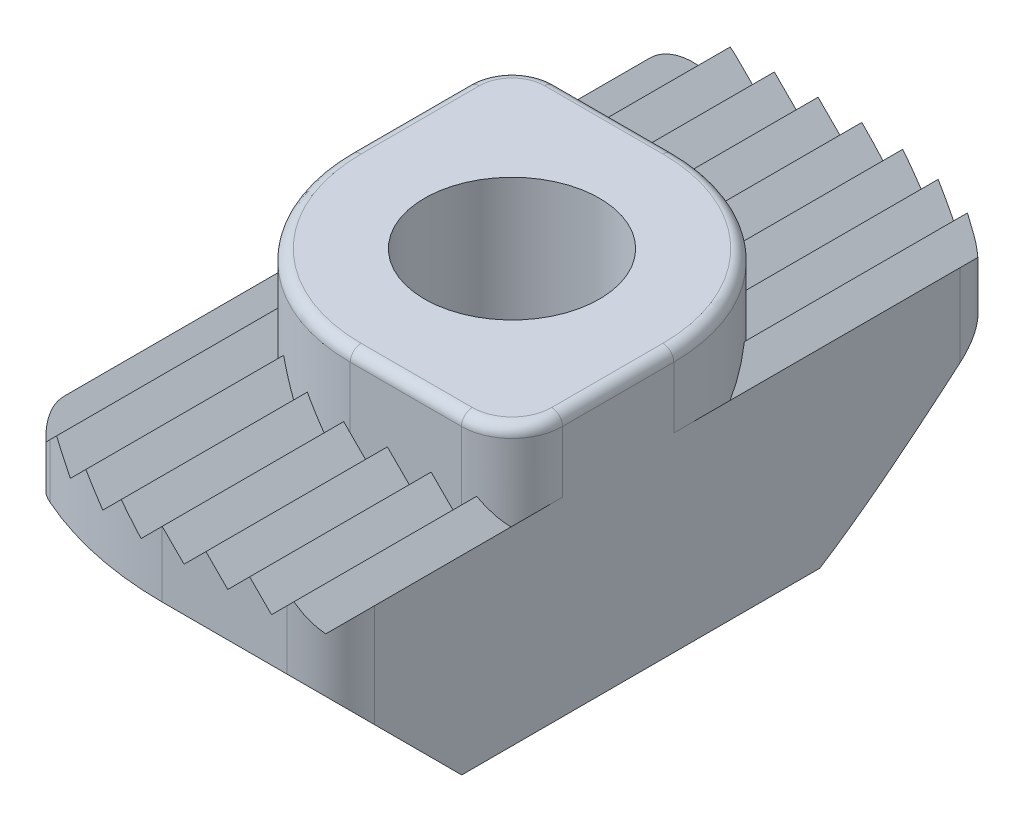
SolidWorks part; units mm, degrees
material "AISI 1020"
ref_plane "Front Plane" through (0, 0, 0) normal (0, 0, 1) x (1, 0, 0)
ref_plane "Top Plane" through (0, 0, 0) normal (0, 1, 0) x (1, 0, 0)
ref_plane "Right Plane" through (0, 0, 0) normal (1, 0, 0) x (0, 0, -1)
sketch "Sketch1" plane through (0, 0, 0) normal (0, 1, 0) x (1, 0, 0)
  line L0 (0, -8) -> (2.85, -8)
  line L1 (3.85, -7) -> (3.85, 6.3936)
  line L2 (0, 8) -> (-2.85, 8)
  line L3 (-3.85, 7) -> (-3.85, -6.3936)
  arc A0 (-3.85, -6.3936) -> (-3.2571, -7.3069) centre (-2.85, -6.3936) ccw
  arc A1 (-3.2571, -7.3069) -> (0, -8) centre (0, 0) ccw
  arc A2 (2.85, -8) -> (3.85, -7) centre (2.85, -7) ccw
  arc A3 (3.85, 6.3936) -> (3.2571, 7.3069) centre (2.85, 6.3936) ccw
  arc A4 (3.2571, 7.3069) -> (0, 8) centre (0, 0) ccw
  arc A5 (-2.85, 8) -> (-3.85, 7) centre (-2.85, 7) ccw
extrude "Extrude1" add sketch "Sketch1" along normal blind 4.5
sketch "Sketch2" plane through (0, 0, 0) normal (0, 0, 1) x (1, 0, 0)
  line L0 (-4, 4.5) -> (-3.5, 4)
  line L1 (-3.5, 4) -> (-3, 4.5)
  line L2 (-3, 4.5) -> (-2.5, 4)
  line L3 (-2.5, 4) -> (-2, 4.5)
  line L4 (-2, 4.5) -> (-1.5, 4)
  line L5 (-1.5, 4) -> (-1, 4.5)
  line L6 (-1, 4.5) -> (-0.5, 4)
  line L7 (-0.5, 4) -> (0, 4.5)
  line L8 (0, 4.5) -> (0.5, 4)
  line L9 (0.5, 4) -> (1, 4.5)
  line L10 (1, 4.5) -> (1.5, 4)
  line L11 (1.5, 4) -> (2, 4.5)
  line L12 (2, 4.5) -> (2.5, 4)
  line L13 (2.5, 4) -> (3, 4.5)
  line L14 (3, 4.5) -> (3.5, 4)
  line L15 (3.5, 4) -> (4, 4.5)
  line L16 (4, 4.5) -> (4, 5.5)
  line L17 (4, 5.5) -> (-4, 5.5)
  line L18 (-4, 5.5) -> (-4, 4.5)
extrude "Cut-Extrude1" cut sketch "Sketch2" against normal blind 8 and the other way blind 8
sketch "Sketch3" plane through (0, 0, 0) normal (0, 1, 0) x (1, 0, 0)
  line L0 (0.15, -3.85) -> (2.6933, -3.85)
  line L1 (3.85, -2.6933) -> (3.85, -0.15)
  line L2 (-0.15, 3.85) -> (-2.85, 3.85)
  line L3 (-3.85, 2.85) -> (-3.85, 0.15)
  arc A0 (-3.85, 0.15) -> (0.15, -3.85) centre (0.15, 0.15) ccw
  arc A1 (2.6933, -3.85) -> (3.85, -2.6933) centre (2.6933, -2.6933) ccw
  arc A2 (3.85, -0.15) -> (-0.15, 3.85) centre (-0.15, -0.15) ccw
  arc A3 (-2.85, 3.85) -> (-3.85, 2.85) centre (-2.85, 2.85) ccw
extrude "Extrude2" add sketch "Sketch3" along normal blind 6.0004
sketch "Sketch4" plane through (0, 0, 0) normal (1, 0, 0) x (0, 0, -1)
  line L0 (-9, -1) -> (9, -1)
  line L1 (9, -1) -> (9, 4)
  line L2 (9, 4) -> (5, 0)
  line L3 (5, 0) -> (-5, 0)
  line L4 (-5, 0) -> (-9, 4)
  line L5 (-9, 4) -> (-9, -1)
extrude "Cut-Extrude2" cut sketch "Sketch4" against normal blind 4 and the other way blind 4
sketch "Sketch5" plane through (0, 0, 0) normal (1, 0, 0) x (0, 0, -1)
  line L0 (0, -1) -> (-9, -1)
  line L1 (-9, -1) -> (-9, 3)
  line L2 (-9, 3) -> (-8, 3)
  line L3 (-8, 3) -> (-5, 0)
  line L4 (-5, 0) -> (0, 0)
  line L5 (0, 0) -> (0, -1)
  line L6 (0, 3) -> (0, -1) construction
revolve "Cut-Revolve1" cut sketch "Sketch5" angle 60 about L6
sketch "Sketch6" plane through (0, 0, 0) normal (1, 0, 0) x (0, 0, -1)
  line L0 (0, 0) -> (5, 0)
  line L1 (5, 0) -> (8, 3)
  line L2 (8, 3) -> (9, 3)
  line L3 (9, 3) -> (9, -1)
  line L4 (9, -1) -> (0, -1)
  line L5 (0, -1) -> (0, 0)
  line L6 (0, -1) -> (0, 3) construction
revolve "Cut-Revolve2" cut sketch "Sketch6" angle 60 about L6 reverse direction yes
sketch "Sketch9" plane through (0, 6.0004, 0) normal (0, 1, 0) x (1, 0, 0)
  circle A0 centre (0, 0) radius 2.4879
extrude "Cut-Extrude3" cut sketch "Sketch9" against normal through all
fillet "Fillet4" radius 0.25 8 edges at (3.5112, 6.0004, 3.5112) (1.4217, 6.0004, 3.85) (-2.6784, 6.0004, 2.6784) (-3.85, 6.0004, -1.5) (-3.5571, 6.0004, -3.5571) (-1.5, 6.0004, -3.85) (2.6784, 6.0004, -2.6784) (3.85, 6.0004, 1.4217)
sketch "Sketch10" plane through (0, 6.0004, 0) normal (0, 1, 0) x (1, 0, 0)
  circle A0 centre (0, 0) radius 2.4879
extrude "Extrude3" add sketch "Sketch10" against normal up to surface (6.0004 mm away) up to face at (0, 0, 2.4879)
sketch "Sketch12" plane through (0, 6.0004, 0) normal (0, 1, 0) x (1, 0, 0)
  circle A0 centre (0, 0) radius 2
  dimension "D1" = 4
extrude "Cut-Extrude4" cut sketch "Sketch12" against normal through all
